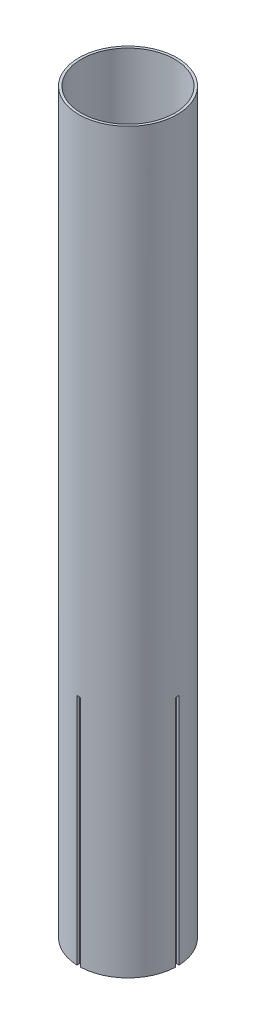
SolidWorks part; units mm, degrees
ref_plane "Front Plane" through (0, 0, 0) normal (0, 0, 1) x (1, 0, 0)
ref_plane "Top Plane" through (0, 0, 0) normal (0, 1, 0) x (1, 0, 0)
ref_plane "Right Plane" through (0, 0, 0) normal (1, 0, 0) x (0, 0, -1)
sketch "Sketch1" plane through (0, 0, 0) normal (0, 1, 0) x (1, 0, 0)
  circle A0 centre (0, 0) radius 38
  circle A1 centre (0, 0) radius 40
  dimension "D1" = 80
  dimension "D2" = 2
extrude "Boss-Extrude1" add sketch "Sketch1" along normal blind 600
sketch "Sketch2" plane through (0, 0, 0) normal (1, 0, 0) x (0, 0, -1)
  line L0 (-40, 0) -> (40, 0) construction
  line L1 (1.5, 190) -> (-1.5, 190)
  line L2 (1.5, 190) -> (1.5, 0)
  line L3 (1.5, 0) -> (-1.5, 0)
  line L4 (-1.5, 190) -> (-1.5, 0)
  line L5 (1.5, 190) -> (-1.5, 0) construction
  line L6 (1.5, 0) -> (-1.5, 190) construction
  point P0 (0, 95)
  point P7 (0, 0)
  point P9 (1.5, 180)
  dimension "D1" = 3
  dimension "D2" = 190
extrude "Cut-Extrude1" cut sketch "Sketch2" against normal through all
pattern_circular "CirPattern1" count 4 over 360 about axis through (0, 600, 0) along (0, -1, 0) of "Cut-Extrude1"
